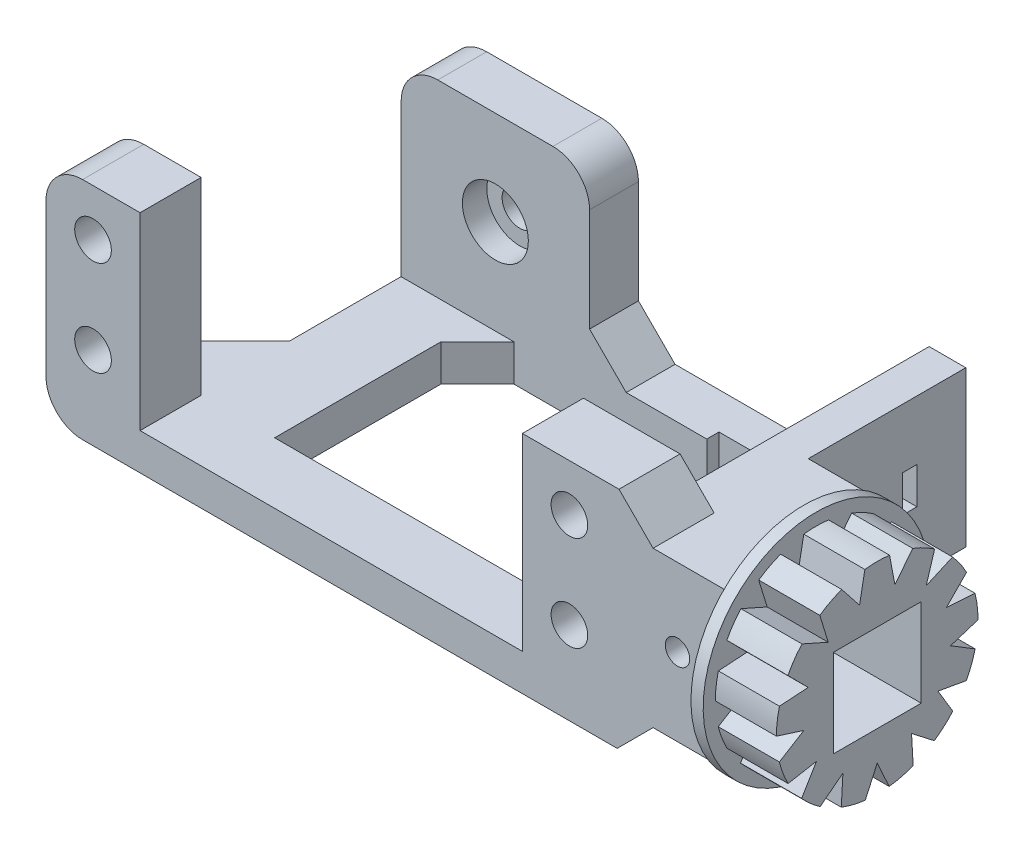
SolidWorks part; units mm, degrees
ref_plane "Front Plane" through (0, 0, 0) normal (0, 0, 1) x (1, 0, 0)
ref_plane "Top Plane" through (0, 0, 0) normal (0, 1, 0) x (1, 0, 0)
ref_plane "Right Plane" through (0, 0, 0) normal (1, 0, 0) x (0, 0, -1)
sketch "Sketch1" plane through (0, 0, 0) normal (0, 0, 1) x (1, 0, 0)
  line L0 (44.6405, 34.4292) -> (44.6405, -27.475) construction
  line L1 (0, 0) -> (39.751, 0)
  line L2 (0, 0) -> (0, 19.558)
  line L3 (0, 19.558) -> (39.751, 19.558)
  line L4 (39.751, 0) -> (39.751, 19.558)
  line L5 (-12.7, 23.368) -> (52.451, 23.368)
  line L6 (-12.7, 23.368) -> (-12.7, -3.81)
  line L7 (-12.7, -3.81) -> (52.451, -3.81)
  line L8 (52.451, 23.368) -> (52.451, -3.81)
  line L9 (-4.8895, 4.826) -> (-4.8895, 32.1367) construction
  line L10 (0, 9.779) -> (87.737, 9.779) construction
  circle A0 centre (-4.8895, 14.732) radius 1.905
  circle A1 centre (-4.8895, 4.826) radius 1.905
  circle A2 centre (44.6405, 14.732) radius 1.905
  circle A3 centre (44.6405, 4.826) radius 1.905
  point P19 (19.8755, 23.368)
  dimension "D7" = 3.81
  dimension "D8" = 3.81
  dimension "D9" = 3.81
  dimension "D10" = 3.81
  dimension "D11" = 9.906
  dimension "D12" = 9.906
  dimension "D13" = 49.53
  dimension "D15" = 4.953
  dimension "D16" = 4.953
  dimension "D1" = 39.751
  dimension "D2" = 19.558
  dimension "D3" = 12.7
  dimension "D4" = 12.7
  dimension "D5" = 3.81
  dimension "D6" = 3.81
  dimension "D14" = 24.765
extrude "Boss-Extrude1" add sketch "Sketch1" along normal blind 6.35
sketch "Sketch2" plane through (0, 0, 6.35) normal (0, 0, 1) x (1, 0, 0)
  line L0 (39.751, 0) -> (39.751, 19.558) construction
  line L1 (0, 19.558) -> (39.751, 19.558)
  line L2 (0, 19.558) -> (0, 29.8051)
  line L3 (0, 29.8051) -> (39.751, 29.8051)
  line L4 (39.751, 19.558) -> (39.751, 29.8051)
extrude "Cut-Extrude1" cut sketch "Sketch2" against normal through all
sketch "Sketch3" plane through (0, 0, 6.35) normal (0, 0, 1) x (1, 0, 0)
  line L0 (52.451, -3.81) -> (52.451, 23.368) construction
  line L1 (-12.7, -3.81) -> (52.451, -3.81)
  line L2 (-12.7, -3.81) -> (-12.7, 0)
  line L3 (-12.7, 0) -> (52.451, 0)
  line L4 (52.451, -3.81) -> (52.451, 0)
extrude "Boss-Extrude2" add sketch "Sketch3" against normal blind 27.432
sketch "Sketch4" plane through (0, 0, 6.35) normal (0, 0, 1) x (1, 0, 0)
  line L0 (-9.779, 19.6215) -> (49.53, 19.6215)
  line L2 (-12.7, 19.6215) -> (-12.7, -7.4902)
  line L3 (-12.7, -7.4902) -> (-9.779, -7.4902)
  line L4 (-9.779, 19.6215) -> (-9.779, -7.4902)
  line L6 (52.451, 19.6215) -> (52.451, -10.7615)
  line L7 (52.451, -10.7615) -> (49.53, -10.7615)
  line L8 (49.53, 19.6215) -> (49.53, -10.7615)
  line L9 (-19.143, 27.8452) -> (59.1863, 27.8452)
  line L10 (-19.143, 27.8452) -> (-19.143, 19.6215)
  line L11 (-19.143, 19.6215) -> (-12.7, 19.6215)
  line L12 (59.1863, 27.8452) -> (59.1863, 19.6215)
  line L13 (52.451, 19.6215) -> (59.1863, 19.6215)
  circle A0 centre (-4.8895, 14.732) radius 1.905 construction
  circle A1 centre (44.6405, 14.732) radius 1.905 construction
  dimension "D1" = 4.8895
  dimension "D3" = 4.8895
  dimension "D2" = 4.8895
extrude "Cut-Extrude2" cut sketch "Sketch4" against normal through all both and the other way through all
sketch "Sketch5" plane through (0, 0, -21.082) normal (0, 0, -1) x (-1, 0, 0)
  line L1 (-49.53, -3.81) -> (9.779, -3.81)
  line L2 (-49.53, -3.81) -> (-49.53, 19.6215)
  line L3 (-49.53, 19.6215) -> (9.779, 19.6215)
  line L4 (9.779, -3.81) -> (9.779, 19.6215)
extrude "Boss-Extrude3" add sketch "Sketch5" along normal blind 5.08
sketch "Sketch6" plane through (0, 0, -26.162) normal (0, 0, -1) x (-1, 0, 0)
  line L0 (9.779, -3.81) -> (9.779, 19.6215) construction
  line L1 (9.779, 19.6215) -> (-49.53, 19.6215) construction
  circle A0 centre (-9.5098, 9.8273) radius 1.8415
  circle A1 centre (-9.5098, 9.8273) radius 6.35
  dimension "D1" = 3.683
  dimension "D2" = 19.2888
  dimension "D3" = 12.7
  dimension "D4" = 9.7942
extrude "Boss-Extrude4" add sketch "Sketch6" along normal blind 2.54
sketch "Sketch7" plane through (0, 0, -26.162) normal (0, 0, -1) x (-1, 0, 0)
  circle A0 centre (-9.5098, 9.8273) radius 1.8415
extrude "Cut-Extrude3" cut sketch "Sketch7" against normal through all both and the other way through all
sketch "Sketch8" plane through (0, 0, -21.082) normal (0, 0, 1) x (1, 0, 0)
  circle A0 centre (9.5098, 9.8273) radius 3.429
  dimension "D1" = 6.858
extrude "Cut-Extrude4" cut sketch "Sketch8" against normal blind 2.54
sketch "Sketch9" plane through (0, 0, -26.162) normal (0, 0, -1) x (-1, 0, 0)
  line L0 (-29.2948, 19.6215) -> (-29.2948, 19.8755) construction
  line L4 (9.779, 19.6215) -> (-49.53, 19.6215) construction
  line L11 (-29.2948, 25.2095) -> (-20.6277, 25.2095) construction
  line L16 (-29.2948, 19.6215) -> (-29.2948, 21.3995) construction
  line L17 (-35.6448, 19.6215) -> (-35.6448, 35.2425)
  line L18 (-29.2948, 25.2095) -> (-29.2948, 28.829) construction
  line L19 (-22.9448, 19.6215) -> (-22.9448, 25.2095)
  line L20 (-29.2948, 32.4485) -> (-22.1011, 32.4485) construction
  line L21 (-30.6918, 37.7825) -> (-27.8978, 37.7825)
  line L22 (-30.6918, 37.7825) -> (-30.6918, 36.2585)
  line L23 (-30.6918, 36.2585) -> (-27.8978, 36.2585)
  line L24 (-27.8978, 37.7825) -> (-27.8978, 36.2585)
  line L25 (-30.6918, 37.7825) -> (-27.8978, 36.2585) construction
  line L26 (-30.6918, 36.2585) -> (-27.8978, 37.7825) construction
  line L27 (-29.2948, 25.2095) -> (-29.2948, 35.2425) construction
  line L28 (-22.9448, 28.829) -> (-22.9448, 35.2425)
  line L29 (-22.9448, 28.829) -> (-22.9448, 25.2095)
  circle A6 centre (-29.2948, 28.829) radius 3.6195
  circle A7 centre (-9.5098, 9.8273) radius 1.8415 construction
  arc A8 (-35.6448, 19.6215) -> (-22.9448, 19.6215) centre (-29.2948, 19.6215) ccw
  arc A9 (-22.9448, 35.2425) -> (-35.6448, 35.2425) centre (-29.2948, 35.2425) ccw
  point P4 (-27.3434, -8.5407)
  point P5 (-29.6455, 24.2252)
  point P7 (-29.6455, 27.432)
  point P11 (-27.3434, -5.08)
  point P13 (-29.2948, 20.6375)
  point P24 (-29.2948, 37.0205)
  point P32 (-29.2948, 41.5925)
  dimension "D1" = 3.81
  dimension "D2" = 7.239
  dimension "D7" = 27.432
  dimension "D8" = 3.81
  dimension "D3" = 9.2075
  dimension "D6" = 6.35
  dimension "D4" = 1.524
  dimension "D5" = 2.794
extrude "Boss-Extrude5" add sketch "Sketch9" against normal blind 3.81
sketch "Sketch10" plane through (0, -3.81, 0) normal (0, -1, 0) x (1, 0, 0)
  line L1 (7.6427, 0) -> (39.751, 0)
  line L3 (7.6427, -21.082) -> (39.751, -21.082)
  line L4 (39.751, 0) -> (39.751, -21.082)
  line L5 (49.53, -26.162) -> (-9.779, -26.162) construction
  line L6 (-9.779, 6.35) -> (-9.779, -26.162) construction
  line L8 (9.5098, -28.702) -> (9.5098, -36.5427) construction
  line L10 (39.751, 6.35) -> (39.751, 0) construction
  line L11 (-9.779, -21.082) -> (49.53, -21.082) construction
  line L12 (39.751, 0) -> (49.53, 0) construction
  line L13 (3.1598, -28.702) -> (15.8598, -28.702) construction
  line L15 (-9.779, 0) -> (-9.779, -26.162)
  line L16 (-9.779, -26.162) -> (-0.2946, -26.162)
  line L17 (7.6427, -21.082) -> (7.6427, 0)
  line L18 (-0.2946, -26.162) -> (-0.2946, -21.082)
  line L20 (-0.2946, -21.082) -> (-0.2946, 0)
  line L21 (-0.2946, 0) -> (-9.779, 0)
  dimension "D1" = 9.8044
  dimension "D2" = 6.35
extrude "Cut-Extrude5" cut sketch "Sketch10" against normal through all both and the other way through all
sketch "Sketch12" plane through (49.53, 0, 0) normal (1, 0, 0) x (0, 0, -1)
  line L0 (-6.35, 19.6215) -> (-6.35, -3.81) construction
  line L1 (-2.8577, 12.573) -> (6.2863, 12.573)
  line L2 (-41.3003, 8.001) -> (-12.4333, 8.001) construction
  line L3 (26.162, -3.81) -> (-6.35, -3.81) construction
  line L8 (6.2865, 12.2682) -> (6.2865, 12.2654)
  line L15 (1.7143, 18.3261) -> (1.7143, -2.3368) construction
  line L17 (1.7143, 8.001) -> (12.6873, 8.001) construction
  line L34 (-2.8577, 12.573) -> (-2.8577, 3.429)
  line L36 (1.7143, 8.001) -> (12.6873, 8.001) construction
  line L49 (1.7143, 18.3261) -> (1.7143, -2.3368) construction
  line L50 (13.3223, 8.001) -> (41.879, 8.001) construction
  line L51 (1.7143, -6.1468) -> (1.7143, -13.8789) construction
  line L54 (6.2865, 12.2682) -> (6.2865, 12.2654)
  line L55 (-2.8577, 3.429) -> (6.2863, 3.429)
  line L56 (6.2863, 12.573) -> (6.2863, 3.429)
  line L57 (-2.8577, 12.573) -> (6.2863, 3.429) construction
  line L58 (-2.8577, 3.429) -> (6.2863, 12.573) construction
  line L59 (9.7786, 16.0782) -> (-6.35, 16.0782)
  line L60 (9.7786, 16.0782) -> (9.7786, -0.0762)
  line L61 (9.7786, -0.0762) -> (-6.35, -0.0762)
  line L62 (-6.35, 16.0782) -> (-6.35, -0.0762)
  line L63 (9.7786, 16.0782) -> (-6.35, -0.0762) construction
  line L64 (9.7786, -0.0762) -> (-6.35, 16.0782) construction
  point P0 (1.7145, 7.9946)
  point P17 (1.7145, 8.001)
  dimension "D2" = 9.144
  dimension "D4" = 3.5052
  dimension "D1" = 9.144
  dimension "D3" = 11.811
extrude "Boss-Extrude8" add sketch "Sketch12" along normal blind 12.7
chamfer "Chamfer1" distance 3.81 angle 45 3 edges at (49.53, 0, -4.8893) (49.53, -0.0762, -1.7143) (49.53, 16.0782, 3.175)
sketch "Sketch13" plane through (49.53, 0, 0) normal (1, 0, 0) x (0, 0, -1)
  line L1 (9.7786, 16.0782) -> (26.162, 16.0782)
  line L2 (9.7786, 16.0782) -> (9.7786, -3.81)
  line L3 (9.7786, -3.81) -> (26.162, -3.81)
  line L4 (26.162, 16.0782) -> (26.162, -3.81)
extrude "Boss-Extrude9" add sketch "Sketch13" along normal blind 3.81
chamfer "Chamfer2" distance 3.7338 angle 45 1 edges at (53.34, -3.81, -17.9703)
chamfer "Chamfer3" distance 3.7338 angle 45 1 edges at (49.53, 16.0782, -23.622)
sketch "Sketch14" plane through (0, 0, 6.35) normal (0, 0, 1) x (1, 0, 0)
  line L0 (62.23, 16.0782) -> (62.23, -0.0762) construction
  circle A0 centre (55.88, 8.001) radius 1.27
  dimension "D1" = 6.35
  dimension "D2" = 2.54
extrude "Cut-Extrude7" cut sketch "Sketch14" against normal through all both and the other way through all
sketch "Sketch15" plane through (0, 0, -26.162) normal (0, 0, -1) x (-1, 0, 0)
  line L0 (0.2946, 19.6215) -> (-22.9448, 19.6215) construction
  line L1 (0.2845, 19.6215) -> (16.235, 19.6215)
  line L2 (0.2845, 19.6215) -> (0.2845, -6.3833)
  line L3 (0.2845, -6.3833) -> (16.235, -6.3833)
  line L4 (16.235, 19.6215) -> (16.235, -6.3833)
  line L5 (-49.6062, -3.81) -> (0.2946, -3.81) construction
  line L6 (-19.304, 14.5415) -> (-44.6405, 14.5415)
  line L7 (-19.304, 14.5415) -> (-19.304, 1.27)
  line L8 (-19.304, 1.27) -> (-44.6405, 1.27)
  line L9 (-44.6405, 14.5415) -> (-44.6405, 1.27)
  circle A0 centre (-9.5098, 9.8273) radius 6.35 construction
  dimension "D1" = 9.7942
  dimension "D2" = 9.7942
  dimension "D3" = 5.08
  dimension "D4" = 5.08
  dimension "D5" = 5.08
extrude "Cut-Extrude8" cut sketch "Sketch15" against normal blind 5.08
chamfer "Chamfer4" distance 9.525 angle 45 1 edges at (-0.2946, -1.905, 0)
fillet "Fillet1" radius 3.81 3 edges at (-9.779, -3.81, 3.1547) (-9.779, 19.6215, 3.175) (-0.2845, 19.6215, -23.622)
sketch "Sketch16" plane through (0, 0, -26.162) normal (0, 0, -1) x (-1, 0, 0)
  line L0 (-19.304, 1.27) -> (-19.304, 14.5415) construction
  line L1 (-49.53, 1.27) -> (-19.304, 1.27)
  line L2 (-49.53, 1.27) -> (-49.53, 16.0782)
  line L3 (-49.53, 48.7008) -> (-19.304, 48.7008)
  line L4 (-19.304, 1.27) -> (-19.304, 48.7008)
  line L5 (-53.34, -0.0762) -> (-53.34, 16.0782) construction
  line L6 (-49.53, 22.932) -> (-49.53, 48.7008)
  line L7 (-53.34, 16.0782) -> (-49.53, 16.0782)
  line L8 (-53.34, 16.0782) -> (-53.34, 22.932)
  line L9 (-53.34, 22.932) -> (-49.53, 22.932)
  dimension "D1" = 3.81
extrude "Cut-Extrude9" cut sketch "Sketch16" against normal blind 6.35
chamfer "Chamfer6" distance 3.81 angle 45 2 edges at (49.53, 0, -15.4303) (7.6427, -1.905, -21.082)
fillet "Fillet2" radius 3.81 1 edges at (19.304, 19.6215, -23.622)
chamfer "Chamfer7" distance 3.81 angle 45 1 edges at (19.304, 1.27, -23.622)
sketch "Sketch17" plane through (0, 1.27, 0) normal (0, 1, 0) x (1, 0, 0)
  line L0 (46.99, 21.082) -> (23.114, 21.082) construction
  line L1 (31.4903, 21.082) -> (35.3003, 21.082)
  line L2 (31.4903, 21.082) -> (31.4903, 22.352)
  line L3 (31.4903, 22.352) -> (35.3003, 22.352)
  line L4 (35.3003, 21.082) -> (35.3003, 22.352)
  dimension "D1" = 1.27
  dimension "D2" = 3.81
extrude "Cut-Extrude10" cut sketch "Sketch17" against normal through all both and the other way through all
sketch "Sketch18" plane through (62.23, 0, 0) normal (1, 0, 0) x (0, 0, -1)
  line L0 (1.7143, 8.001) -> (1.7143, 12.573) construction
  line L1 (2.998, 18.3996) -> (3.5523, 15.458)
  line L2 (0.4306, 18.3996) -> (-0.1237, 15.458)
  line L3 (0.4306, 18.3996) -> (1.7143, 18.4906) construction
  line L4 (1.7143, 8.001) -> (3.3306, 12.3161) construction
  line L6 (-2.8577, 12.573) -> (6.2863, 12.573) construction
  line L7 (1.7143, 8.001) -> (-2.8577, 8.001) construction
  line L9 (-2.8577, 12.573) -> (-2.8577, 3.429) construction
  line L10 (1.7143, 3.429) -> (1.7143, 12.573) construction
  line L11 (-2.8577, 3.429) -> (6.2863, 3.429) construction
  line L12 (7.6835, 16.6119) -> (6.8072, 13.7497)
  line L14 (5.41, 17.8051) -> (3.5523, 15.458)
  line L15 (11.0014, 12.8515) -> (8.8953, 10.7244)
  line L17 (9.5429, 14.9646) -> (6.8072, 13.7497)
  line L18 (12.1918, 7.98) -> (9.3384, 7.0753)
  line L20 (11.8823, 10.5288) -> (8.8953, 10.7244)
  line L21 (10.9819, 3.1133) -> (8.0349, 3.6382)
  line L23 (11.8923, 5.5139) -> (9.3384, 7.0753)
  line L24 (7.6489, -0.6337) -> (5.2834, 1.2006)
  line L26 (9.5707, 1.0689) -> (8.0349, 3.6382)
  line L27 (2.9564, -2.4026) -> (1.7143, 0.3209)
  line L29 (5.4493, -1.7882) -> (5.2834, 1.2006)
  line L30 (-2.0207, -1.7882) -> (-1.8548, 1.2006)
  line L32 (0.4722, -2.4026) -> (1.7143, 0.3209)
  line L33 (-6.1421, 1.0689) -> (-4.6063, 3.6382)
  line L35 (-4.2203, -0.6337) -> (-1.8548, 1.2006)
  line L36 (-8.4637, 5.5139) -> (-5.9098, 7.0753)
  line L38 (-7.5533, 3.1133) -> (-4.6063, 3.6382)
  line L39 (-8.4537, 10.5288) -> (-5.4667, 10.7244)
  line L41 (-8.7632, 7.98) -> (-5.9098, 7.0753)
  line L42 (-6.1143, 14.9646) -> (-3.3786, 13.7497)
  line L44 (-7.5728, 12.8515) -> (-5.4667, 10.7244)
  line L45 (-1.9814, 17.8051) -> (-0.1237, 15.458)
  line L47 (-4.2549, 16.6119) -> (-3.3786, 13.7497)
  line L48 (1.7143, 18.4785) -> (1.7143, 18.4906) construction
  line L49 (1.7143, 25.2132) -> (1.7143, 26.3686) construction
  line L54 (-2.8577, 12.573) -> (6.2863, 12.573)
  line L55 (-2.8577, 12.573) -> (-2.8577, 3.429)
  line L56 (-2.8577, 3.429) -> (6.2863, 3.429)
  line L57 (6.2863, 12.573) -> (6.2863, 3.429)
  arc A1 (2.998, 18.3996) -> (0.4306, 18.3996) centre (1.7143, 8.001) ccw
  arc A3 (7.6835, 16.6119) -> (5.41, 17.8051) centre (1.7143, 8.001) ccw
  arc A4 (11.0014, 12.8515) -> (9.5429, 14.9646) centre (1.7143, 8.001) ccw
  arc A5 (12.1918, 7.98) -> (11.8823, 10.5288) centre (1.7143, 8.001) ccw
  arc A6 (10.9819, 3.1133) -> (11.8923, 5.5139) centre (1.7143, 8.001) ccw
  arc A7 (7.6489, -0.6337) -> (9.5707, 1.0689) centre (1.7143, 8.001) ccw
  arc A8 (2.9564, -2.4026) -> (5.4493, -1.7882) centre (1.7143, 8.001) ccw
  arc A9 (-2.0207, -1.7882) -> (0.4722, -2.4026) centre (1.7143, 8.001) ccw
  arc A10 (-6.1421, 1.0689) -> (-4.2203, -0.6337) centre (1.7143, 8.001) ccw
  arc A11 (-8.4637, 5.5139) -> (-7.5533, 3.1133) centre (1.7143, 8.001) ccw
  arc A12 (-8.4537, 10.5288) -> (-8.7632, 7.98) centre (1.7143, 8.001) ccw
  arc A13 (-6.1143, 14.9646) -> (-7.5728, 12.8515) centre (1.7143, 8.001) ccw
  arc A14 (-1.9814, 17.8051) -> (-4.2549, 16.6119) centre (1.7143, 8.001) ccw
  point P61 (1.7143, 8.001)
  dimension "D1" = 13
  dimension "D2" = 20.955
  dimension "D3" = 10.67
  dimension "D4" = 10.67
extrude "Boss-Extrude10" add sketch "Sketch18" along normal blind 6.35
sketch "Sketch19" plane through (62.23, 0, 0) normal (-1, 0, 0) x (0, 0, 1)
  line L1 (-6.2863, 12.573) -> (2.8577, 12.573)
  line L2 (-6.2863, 12.573) -> (-6.2863, 3.429)
  line L3 (-6.2863, 3.429) -> (2.8577, 3.429)
  line L4 (2.8577, 12.573) -> (2.8577, 3.429)
  circle A0 centre (-1.7143, 8.001) radius 11.7475
  dimension "D1" = 23.495
extrude "Boss-Extrude11" add sketch "Sketch19" along normal blind 1.27
sketch "Sketch20" plane through (53.34, 0, 0) normal (1, 0, 0) x (0, 0, -1)
  line L0 (26.162, 8.001) -> (18.097, 8.001) construction
  line L1 (26.162, -0.0762) -> (26.162, 16.0782) construction
  line L2 (26.162, 3.4773) -> (26.162, 16.1773) construction
  line L3 (19.558, 9.906) -> (21.082, 9.906)
  line L4 (19.558, 9.906) -> (19.558, 6.096)
  line L5 (19.558, 6.096) -> (21.082, 6.096)
  line L6 (21.082, 9.906) -> (21.082, 6.096)
  line L7 (19.558, 9.906) -> (21.082, 6.096) construction
  line L8 (19.558, 6.096) -> (21.082, 9.906) construction
  point P4 (20.32, 8.001)
  dimension "D1" = 1.524
  dimension "D2" = 3.81
  dimension "D3" = 5.08
extrude "Cut-Extrude11" cut sketch "Sketch20" against normal blind 7.62
